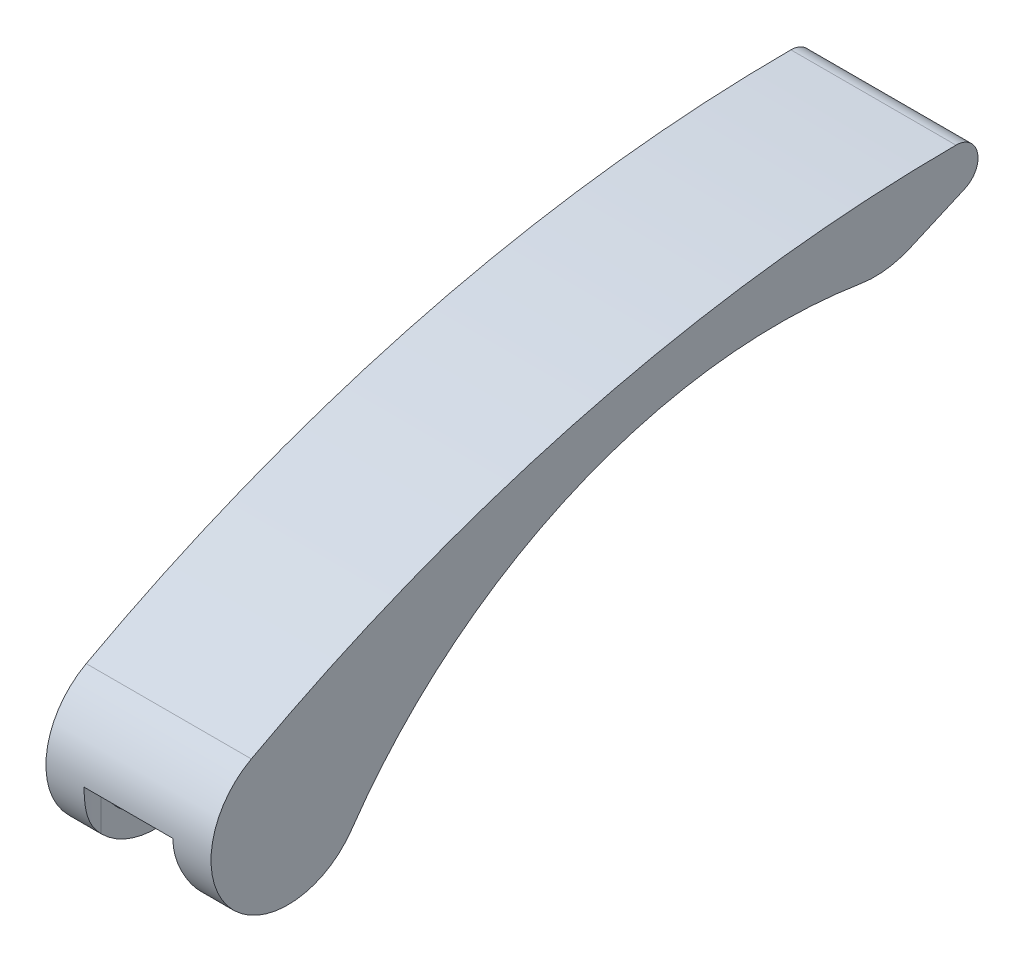
SolidWorks part; units mm, degrees
ref_plane "Front Plane" through (0, 0, 0) normal (0, 0, 1) x (1, 0, 0)
ref_plane "Top Plane" through (0, 0, 0) normal (0, 1, 0) x (1, 0, 0)
ref_plane "Right Plane" through (0, 0, 0) normal (1, 0, 0) x (0, 0, -1)
sketch "Sketch4" plane through (0, 0, 0) normal (1, 0, 0) x (0, 0, -1)
  line L0 (28.2696, 8.2178) -> (30.7464, 9.3031)
  circle A0 centre (0, 0) radius 2.5
  arc A2 (-1.6685, 3.0767) -> (2.8818, -1.9862) centre (0, 0) ccw
  arc A3 (-1.6685, 3.0767) -> (30.3439, 11.219) centre (30.4268, -56.1086) cw
  arc A4 (2.8818, -1.9862) -> (26.035, 7.9313) centre (22.3214, -15.3843) cw
  circle A5 centre (0, 0) radius 3.5 construction
  arc A6 (28.2696, 8.2178) -> (26.035, 7.9313) centre (26.6642, 11.8815) cw
  arc A7 (30.7464, 9.3031) -> (30.3439, 11.219) centre (30.3451, 10.219) ccw
  point P5 (2.8282, -2.0619)
  point P11 (24.2926, 1.6769)
  point P12 (29.4365, 8.103)
  point P13 (3.2805, -1.2199)
  point P14 (-2.4231, 2.5255)
  point P15 (29.7274, 8.6849)
  point P16 (29.9602, 10.0232)
  point P17 (3.221, -1.3693)
  point P18 (24.1994, 7.812)
  point P19 (29.3997, 10.0009)
  point P20 (0, 0)
  point P24 (0, 0)
  point P25 (29.9198, 10.962)
  point P26 (3.1352, -1.5557)
  point P27 (-2.5347, 2.4135)
  point P28 (30.7439, 9.6077)
  point P29 (3.193, -1.4334)
  point P30 (-0.9992, 3.3543)
  point P31 (23.5444, 4.5647)
  point P32 (29.0507, 9.1409)
  point P33 (22.9423, 4.7468)
  point P34 (0, 0)
  point P37 (19.5787, 4.6817)
  point P38 (24.5806, 5.1228)
  point P39 (21.13, 4.535)
  point P40 (24.0815, 5.4203)
  point P41 (27.7449, 7.5603)
  point P42 (28.0404, 7.9739)
  point P43 (26.7754, 7.146)
  point P44 (29.0633, 10.8383)
  point P45 (28.2696, 8.2178)
  dimension "D1" = 5
  dimension "D2" = 1
  dimension "D3" = 4
  dimension "D4" = 1
extrude "Boss-Extrude2" add sketch "Sketch4" along normal blind 7.5 contours A2 A4 L0 A3 A0 region at (0, 8.2892, -27.1248)
sketch "Sketch5" plane through (0, 0, 0) normal (0, 1, 0) x (1, 0, 0)
  line L6 (1.5, -2.5) -> (0, -2.5) construction
  line L7 (6, -2.5) -> (7.5, -2.5) construction
  line L8 (-1, 2.5) -> (6.5, 2.5) construction
  line L10 (7.5, -2.5) -> (0, -2.5) construction
  line L13 (1.5, 2.5) -> (1.5, -2.5)
  line L14 (6, 2.5) -> (6, -2.5)
  arc A1 (1.5, -2.5) -> (6, -2.5) centre (3.75, -2.5) ccw
  arc A2 (1.5, 2.5) -> (6, 2.5) centre (3.75, 2.5) cw
  dimension "D1" = 1.5
  dimension "D2" = 5
extrude "Cut-Extrude1" cut sketch "Sketch5" against normal through all contours L14 A1 L13 A2
extrude "Boss-Extrude4" add sketch "Sketch4<4>" along normal blind 0.5 contours A0
sketch "Sketch4<4>" plane through (0, 0, 0) normal (1, 0, 0) x (0, 0, -1) same geometry as "Sketch4"
extrude "Boss-Extrude5" add sketch "Sketch4<5>" along normal blind 0.5 from offset 7 contours A0 region at (0, 0, 0)
sketch "Sketch4<5>" plane through (0, 0, 0) normal (1, 0, 0) x (0, 0, -1) same geometry as "Sketch4"
